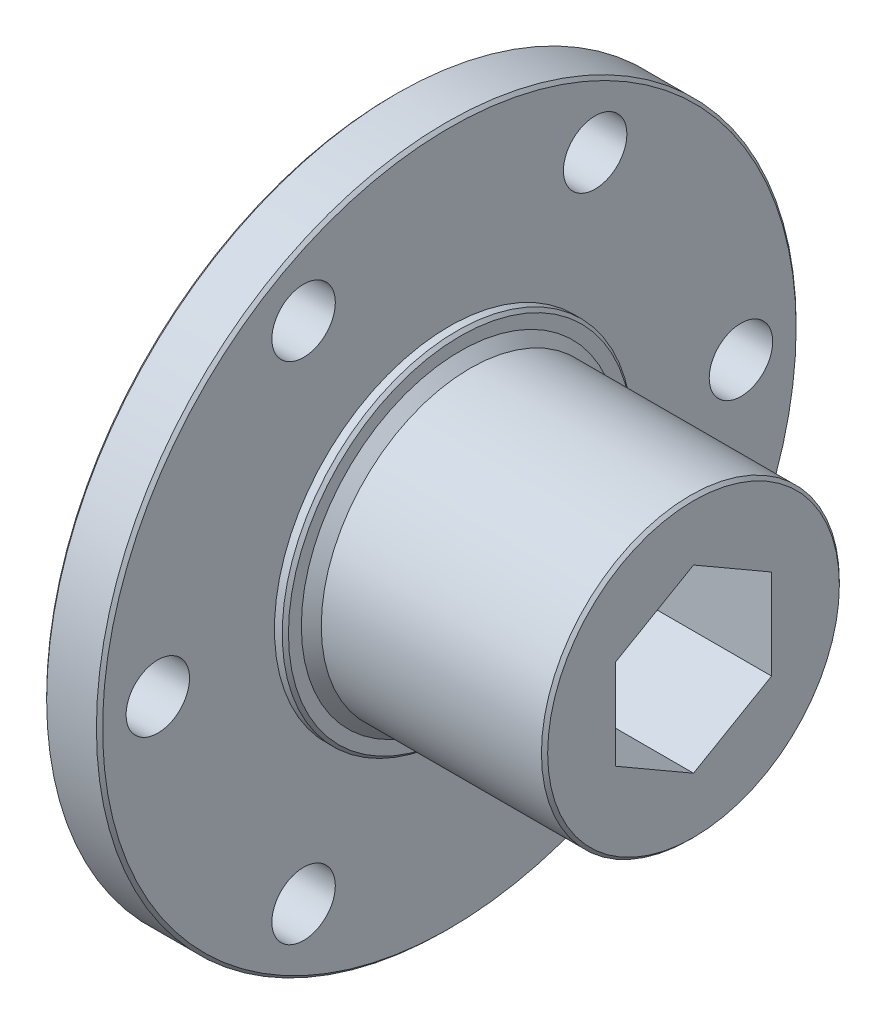
SolidWorks part; units mm, degrees
ref_plane "Front Plane" through (0, 0, 0) normal (0, 0, 1) x (1, 0, 0)
ref_plane "Top Plane" through (0, 0, 0) normal (0, 1, 0) x (1, 0, 0)
ref_plane "Right Plane" through (0, 0, 0) normal (1, 0, 0) x (0, 0, -1)
ref_plane "Plane4" through (0, 0, 0) normal (0, 0, -1) x (-1, 0, 0)
sketch "Sketch1" plane through (0, 0, 0) normal (0, 0, -1) x (-1, 0, 0)
  line L0 (13.9241, 28.575) -> (13.9241, 0)
  line L1 (13.9241, 0) -> (18.4961, 0)
  line L2 (18.4961, 0) -> (18.4961, 28.575)
  line L3 (18.4961, 28.575) -> (13.9241, 28.575)
  line L4 (13.9241, 0) -> (18.4961, 0) construction
revolve "Revolve1" add sketch "Sketch1" angle 360 about L4 reverse direction yes
sketch "Sketch2" plane through (-13.9241, 0, 0) normal (1, 0, 0) x (0, 0, -1)
  circle A0 centre (0, 0) radius 14.2875
extrude "Boss-Extrude1" add sketch "Sketch2" along normal blind 0.889
sketch "Sketch3" plane through (-13.0351, 0, 0) normal (1, 0, 0) x (0, 0, -1)
  circle A0 centre (0, 0) radius 12.9794
extrude "Boss-Extrude2" add sketch "Sketch3" along normal blind 0.8128 draft 45
sketch "Sketch4" plane through (-12.2223, 0, 0) normal (1, 0, 0) x (0, 0, -1)
  circle A0 centre (0, 0) radius 12.1666
extrude "Boss-Extrude3" add sketch "Sketch4" along normal blind 18.2372
sketch "Sketch5" plane through (-18.4961, 0, 0) normal (-1, 0, 0) x (0, 0, 1)
  circle A0 centre (0, 0) radius 14.2875
extrude "Boss-Extrude4" add sketch "Sketch5" along normal blind 0.889
sketch "Sketch6" plane through (-19.3851, 0, 0) normal (-1, 0, 0) x (0, 0, 1)
  line L0 (0, 7.3617) -> (-6.3754, 3.6808)
  line L1 (-6.3754, 3.6808) -> (-6.3754, -3.6809)
  line L2 (-6.3754, -3.6809) -> (0, -7.3617)
  line L3 (0, -7.3617) -> (6.3754, -3.6809)
  line L4 (6.3754, -3.6809) -> (6.3754, 3.6808)
  line L5 (6.3754, 3.6808) -> (0, 7.3617)
extrude "Cut-Extrude1" cut sketch "Sketch6" against normal through all
hole_wizard "#6 (0.204) Diameter Hole1" positions "Sketch8" profile "Sketch7" hole size "#6" standard "ANSI Inch"
sketch "Sketch8" plane through (-18.4961, 0, 0) normal (-1, 0, 0) x (0, 0, 1)
  point P0 (11.9063, 20.6222)
  point P1 (-23.8125, 0)
  point P2 (11.9062, -20.6222)
  point P3 (-11.9063, -20.6222)
  point P4 (-11.9062, 20.6222)
  point P5 (23.8125, 0)
sketch "Sketch7" plane through (-18.4961, 20.6222, 11.9063) normal (0, 1, 0) x (0, 0, 1)
  line L0 (0, 0) -> (0, 24.511)
  line L1 (0, 24.511) -> (2.5908, 24.511)
  line L2 (2.5908, 24.511) -> (2.5908, 0)
  line L5 (2.5908, 0) -> (0, 0)
  line L11 (0, -6.35) -> (0, 107.95) construction
  dimension "Thru Hole Dia." = 5.1816
  dimension "Thru Hole Depth" = 24.511
chamfer "Chamfer1" distance 0.254 angle 45 5 edges at (-19.3851, 0, 14.2875) (6.0149, 0, -12.1666) (-18.4961, 0, 28.575) (-13.0351, 0, -14.2875) (-13.9241, 0, 28.575)
